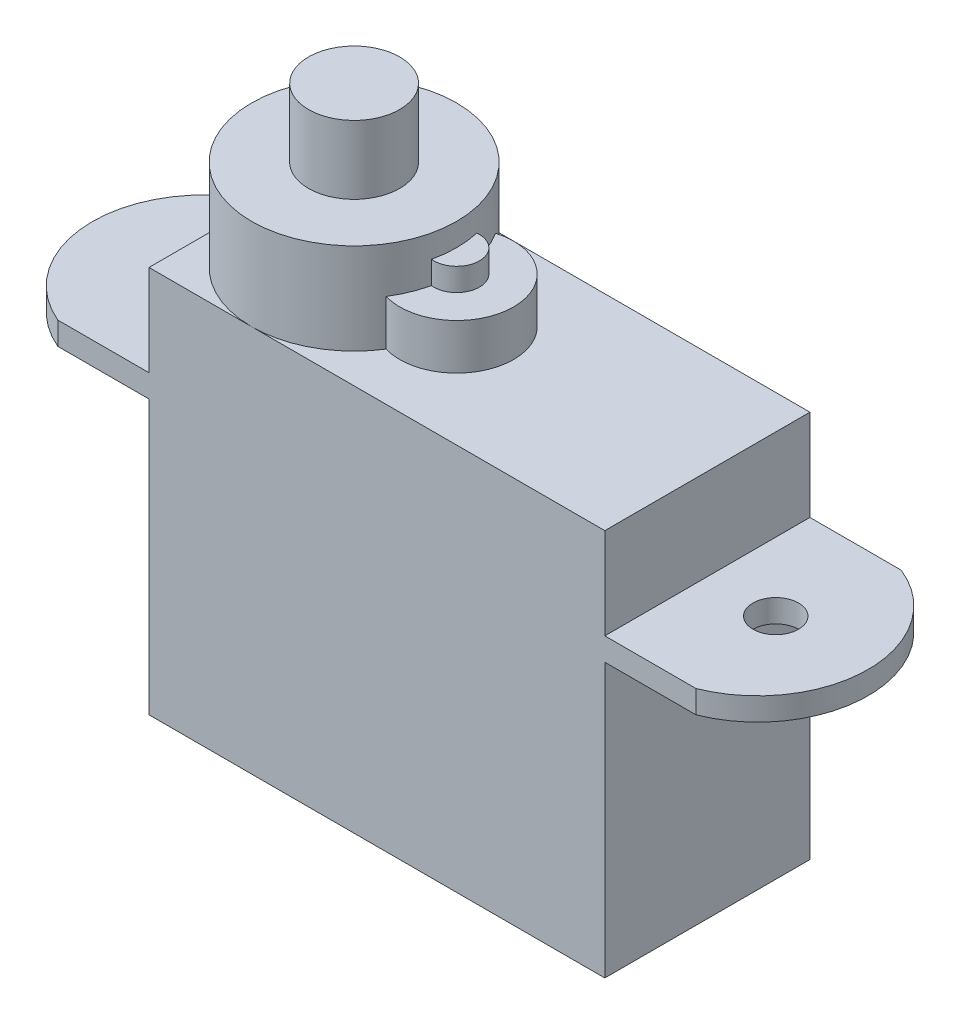
SolidWorks part; units mm, degrees
ref_plane "Front Plane" through (0, 0, 0) normal (0, 0, 1) x (1, 0, 0)
ref_plane "Top Plane" through (0, 0, 0) normal (0, 1, 0) x (1, 0, 0)
ref_plane "Right Plane" through (0, 0, 0) normal (1, 0, 0) x (0, 0, -1)
sketch "Sketch1" plane through (0, 0, 0) normal (0, 1, 0) x (1, 0, 0)
  line L0 (14, 0) -> (17, 0) construction
  line L1 (-10, -4.5) -> (10, -4.5)
  line L2 (-10, -4.5) -> (-10, 4.5)
  line L3 (-10, 4.5) -> (10, 4.5)
  line L4 (10, -4.5) -> (10, 4.5)
  line L5 (-10, -4.5) -> (10, 4.5) construction
  line L6 (-10, 4.5) -> (10, -4.5) construction
  line L7 (-10, -4.5) -> (-14, -4.5)
  line L8 (-10, -4.5) -> (-10, 4.5)
  line L9 (-10, 4.5) -> (-14, 4.5)
  line L10 (-14, -4.5) -> (-14, 4.5)
  line L11 (10, -4.5) -> (14, -4.5)
  line L12 (10, -4.5) -> (10, 4.5)
  line L13 (10, 4.5) -> (14, 4.5)
  line L14 (14, -4.5) -> (14, 4.5)
  line L15 (-14, 0) -> (-17, 0) construction
  line L16 (-10, 0) -> (-13, 0) construction
  line L17 (-10, 0) -> (-5.5, 0) construction
  line L18 (-5.5, 0) -> (-1, 0) construction
  line L20 (10, 0) -> (13, 0) construction
  arc A0 (-14, 4.5) -> (-14, -4.5) centre (-12.1019, 0) ccw
  arc A1 (14, 4.5) -> (14, -4.5) centre (12.212, 0) cw
  circle A2 centre (-5.5, 0) radius 4.5
  circle A3 centre (-1, 0) radius 2.5
  circle A4 centre (-1, 0) radius 1
  circle A5 centre (13, 0) radius 1
  circle A6 centre (-13, 0) radius 1
  circle A7 centre (-5.5, 0) radius 2
  point P0 (0, 0)
  dimension "D1" = 20
  dimension "D2" = 9
  dimension "D3" = 4
  dimension "D4" = 4
extrude "Boss-Extrude3" add sketch "Sketch1" along normal blind 4 and the other way blind 13 contours A3 A2 L1 L4 L3 | A2 L2 L1 | A2 L3 L8 | A3 A7 A2 | A7 | A4 A2 A3 | A4 A2 A3 | A2 A4 | A2 A4 region at (-8.9948, 0, 3.4948) region at (4.4349, 0, 0) region at (-5.5, 0, 0) region at (-8.5954, 0, 3.0954) region at (-8.9948, 0, -3.4948) region at (-2.329, 0, 0) region at (0.0181, 0, 0) region at (-1.4438, 0, 0) region at (-0.5962, 0, 0)
extrude "Boss-Extrude4" add sketch "Sketch1<3>" along normal blind 0.0001 and the other way blind 1 contours L10 A6 L7 L2 L8 L9 | L14 A5 L13 L4 L11 | A1 L14 | L10 A0 region at (-11.9044, 0, 0) region at (-15.2325, 0, 0) region at (11.9044, 0, 0) region at (15.2622, 0, 0)
sketch "Sketch1<3>" plane through (0, 0, 0) normal (0, 1, 0) x (1, 0, 0) same geometry as "Sketch1"
extrude "Boss-Extrude6" add sketch "Sketch1<8>" along normal blind 7 contours A2 A4 | A2 A4 region at (-1.4438, 0, 0) region at (-0.5962, 0, 0)
sketch "Sketch1<8>" plane through (0, 0, 0) normal (0, 1, 0) x (1, 0, 0) same geometry as "Sketch1"
extrude "Boss-Extrude7" add sketch "Sketch1<9>" along normal blind 11 contours A7 region at (-5.5, 0, 0)
sketch "Sketch1<9>" plane through (0, 0, 0) normal (0, 1, 0) x (1, 0, 0) same geometry as "Sketch1"
extrude "Boss-Extrude10" add sketch "Sketch1<11>" along normal blind 8 contours A3 A7 A2 | A7 | A4 A2 A3 | A2 A4 region at (-5.5, 0, 0) region at (-8.5954, 0, 3.0954) region at (-2.329, 0, 0) region at (-1.4438, 0, 0)
sketch "Sketch1<11>" plane through (0, 0, 0) normal (0, 1, 0) x (1, 0, 0) same geometry as "Sketch1"
extrude "Boss-Extrude11" add sketch "Sketch1<12>" along normal blind 6 contours A4 A2 A3 | A2 A4 | A4 A2 A3 | A2 A4 region at (-2.329, 0, 0) region at (0.0181, 0, 0) region at (-1.4438, 0, 0) region at (-0.5962, 0, 0)
sketch "Sketch1<12>" plane through (0, 0, 0) normal (0, 1, 0) x (1, 0, 0) same geometry as "Sketch1"
